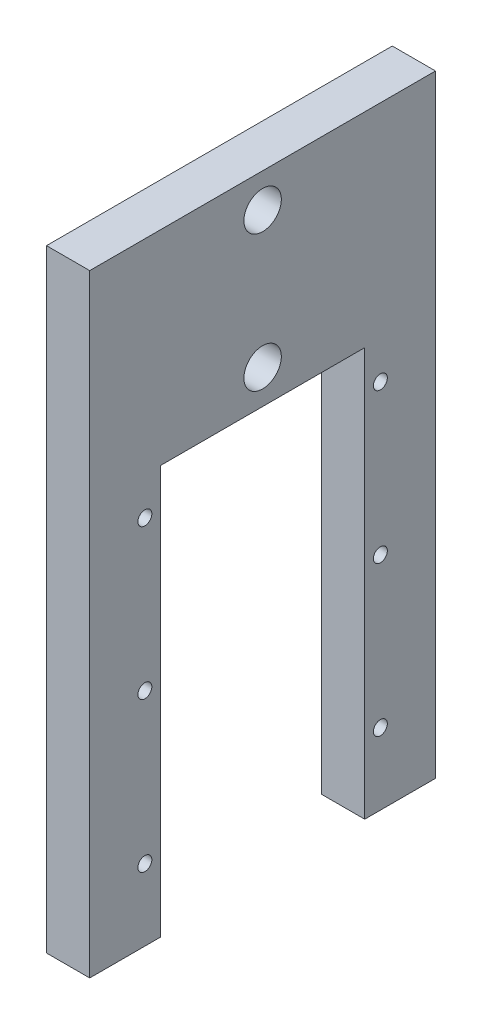
SolidWorks part; units mm, degrees
ref_plane "Front Plane" through (0, 0, 0) normal (0, 0, 1) x (1, 0, 0)
ref_plane "Top Plane" through (0, 0, 0) normal (0, 1, 0) x (1, 0, 0)
ref_plane "Right Plane" through (0, 0, 0) normal (1, 0, 0) x (0, 0, -1)
sketch "Sketch2" plane through (0, 0, 0) normal (0, 0, 1) x (1, 0, 0)
  line L1 (3.175, -45) -> (-3.175, -45)
  line L2 (3.175, -45) -> (3.175, 45)
  line L3 (3.175, 45) -> (-3.175, 45)
  line L4 (-3.175, -45) -> (-3.175, 45)
  line L5 (3.175, -45) -> (-3.175, 45) construction
  line L6 (3.175, 45) -> (-3.175, -45) construction
  point P0 (0, 0)
  dimension "D1" = 90
  dimension "D2" = 6.35
extrude "Boss-Extrude1" add sketch "Sketch2" along normal mid plane 50.8
sketch "Sketch4" plane through (-3.175, 0, 0) normal (-1, 0, 0) x (0, 0, 1)
  line L0 (15, -45) -> (15, 15)
  line L2 (15, 15) -> (-15, 15)
  line L3 (0, 0.0539) -> (0, 22.3365) construction
  line L4 (-15, -45) -> (-15, 15)
  line L5 (-15, -45) -> (15, -45)
  line L6 (25.4, -45) -> (-25.4, -45) construction
  line L7 (25.4, 45) -> (25.4, -45) construction
  line L8 (17.3, -34.5) -> (17.3, -12.5) construction
  line L9 (17.3, -12.5) -> (17.3, 9.5) construction
  circle A0 centre (17.3, -34.5) radius 1.025
  circle A1 centre (-17.3, -34.5) radius 1.025
  circle A2 centre (17.3, -12.5) radius 1.025
  circle A3 centre (-17.3, -12.5) radius 1.025
  circle A4 centre (-17.3, 9.5) radius 1.025
  circle A5 centre (17.3, 9.5) radius 1.025
  point P8 (0, 15)
  dimension "D5" = 2.05
  dimension "D1" = 60
  dimension "D2" = 30
  dimension "D3" = 10.5
  dimension "D4" = 8.1
  dimension "D6" = 22
extrude "Cut-Extrude4" cut sketch "Sketch4" against normal through all contours L0 L2 L4 L5 | A0 | A2 | A5 | A1 | A3 | A4
hole_wizard "M5 Clearance Hole1" positions "Sketch7" profile "Sketch6" hole size "M5" standard "ANSI Metric" end condition up to next
sketch "Sketch7" plane through (-3.175, 0, 0) normal (-1, 0, 0) x (0, 0, 1)
  line L1 (25.4, 45) -> (-25.4, 45) construction
  line L2 (15, 15) -> (15, 45) construction
  line L4 (15, 30) -> (-12.8341, 30) construction
  point P0 (0, 40)
  point P2 (0, 20)
  dimension "D1" = 20
sketch "Sketch6" plane through (-3.175, 40, 0) normal (0, 1, 0) x (0, 0, 1)
  line L0 (0, 0) -> (0, 6.35)
  line L1 (0, 6.35) -> (2.75, 6.35)
  line L2 (2.75, 6.35) -> (2.75, 0)
  line L5 (2.75, 0) -> (0, 0)
  line L11 (0, -6.35) -> (0, 107.95) construction
  dimension "Thru Hole Dia." = 5.5
  dimension "Thru Hole Depth" = 6.35
